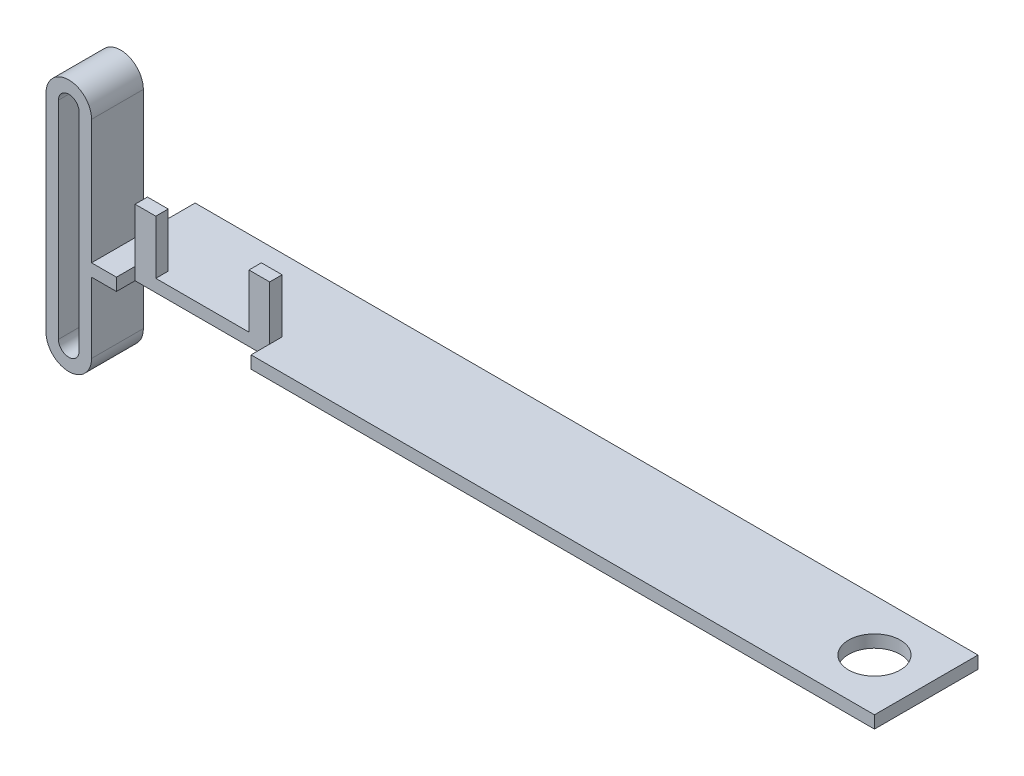
SolidWorks part; units mm, degrees
ref_plane "Front Plane" through (0, 0, 0) normal (0, 0, 1) x (1, 0, 0)
ref_plane "Top Plane" through (0, 0, 0) normal (0, 1, 0) x (1, 0, 0)
ref_plane "Right Plane" through (0, 0, 0) normal (1, 0, 0) x (0, 0, -1)
sketch "Sketch1" plane through (0, 0, 0) normal (0, 1, 0) x (1, 0, 0)
  line L1 (-100, 12.5) -> (100, 12.5)
  line L2 (-100, 12.5) -> (-100, -12.5)
  line L3 (-100, -12.5) -> (100, -12.5)
  line L4 (100, 12.5) -> (100, -12.5)
  line L5 (-100, 12.5) -> (100, -12.5) construction
  line L6 (-100, -12.5) -> (100, 12.5) construction
  circle A4 centre (87.5, 0) radius 6.25
  point P0 (0, 0)
  point P17 (100, 0)
  dimension "D3" = 12.5
  dimension "D4" = 12.5
  dimension "D1" = 25
  dimension "D2" = 200
extrude "Boss-Extrude1" add sketch "Sketch1" along normal blind 3 contours L3 L4 L1 L2 A4 | L3 region at (-2.2016, 0, 0)
sketch "Sketch2" plane through (0, 0, 0) normal (0, 0, 1) x (1, 0, 0)
  line L0 (-94.5, 33) -> (-94.5, -17) construction
  line L1 (-92, 33) -> (-92, -17)
  line L2 (-97, 33) -> (-97, -17)
  line L3 (-89, 33) -> (-89, -17)
  line L4 (-100, 33) -> (-100, -17)
  line L7 (-83, 6.4998) -> (-50.5, 6.4998)
  line L8 (-83, 6.4998) -> (-83, -3.3981)
  line L9 (-83, -3.3981) -> (-50.5, -3.3981)
  line L10 (-50.5, 6.4998) -> (-50.5, -3.3981)
  arc A0 (-92, 33) -> (-97, 33) centre (-94.5, 33) ccw
  arc A1 (-97, -17) -> (-92, -17) centre (-94.5, -17) ccw
  arc A2 (-100, -17) -> (-89, -17) centre (-94.5, -17) ccw
  arc A3 (-89, 33) -> (-100, 33) centre (-94.5, 33) ccw
  point P2 (-94.5, 8)
  dimension "D4" = 5.5
  dimension "D1" = 3
  dimension "D2" = 3
  dimension "D3" = 5
  dimension "D5" = 50
  dimension "D6" = 50
  dimension "D7" = 6
  dimension "D8" = 32.5
extrude "Boss-Extrude2" add sketch "Sketch2" along normal up to surface (12.5 mm away) contours L3 A3 L4 A2 A1 L2 A0 L1 region at (-89.6198, 8, 0) up to face at (0, 1.5, 12.5)
extrude "Cut-Extrude1" cut sketch "Sketch2<2>" against normal through all both and the other way through all contours L2 A1 L1 A0 region at (-94.5, 8, 0)
sketch "Sketch2<2>" plane through (0, 0, 0) normal (0, 0, 1) x (1, 0, 0) same geometry as "Sketch2"
extrude "Cut-Extrude2" cut sketch "Sketch2<3>" against normal up to surface (12.5 mm away) contours L3 A3 L4 A2 A1 L2 A0 L1 region at (-89.6198, 8, 0) up to face at (4, 1.5, -12.5)
sketch "Sketch2<3>" plane through (0, 0, 0) normal (0, 0, 1) x (1, 0, 0) same geometry as "Sketch2"
extrude "Cut-Extrude3" cut sketch "Sketch2<5>" along normal up to surface (12.5 mm away) from offset 8 contours L10 L7 L8 L9 region at (-66.75, 1.5509, 0) up to face at (-94.5, 8, 12.5)
sketch "Sketch2<5>" plane through (0, 0, 0) normal (0, 0, 1) x (1, 0, 0) same geometry as "Sketch2"
sketch "Sketch4" plane through (0, 0, 8) normal (0, 0, 1) x (1, 0, 0)
  line L1 (-83, 3) -> (-78, 3)
  line L2 (-83, 3) -> (-83, 16)
  line L3 (-83, 16) -> (-78, 16)
  line L4 (-78, 3) -> (-78, 16)
  line L5 (-50.5, 3) -> (-55.5, 3)
  line L6 (-50.5, 3) -> (-50.5, 16)
  line L7 (-50.5, 16) -> (-55.5, 16)
  line L8 (-55.5, 3) -> (-55.5, 16)
extrude "Boss-Extrude3" add sketch "Sketch4" against normal blind 3
